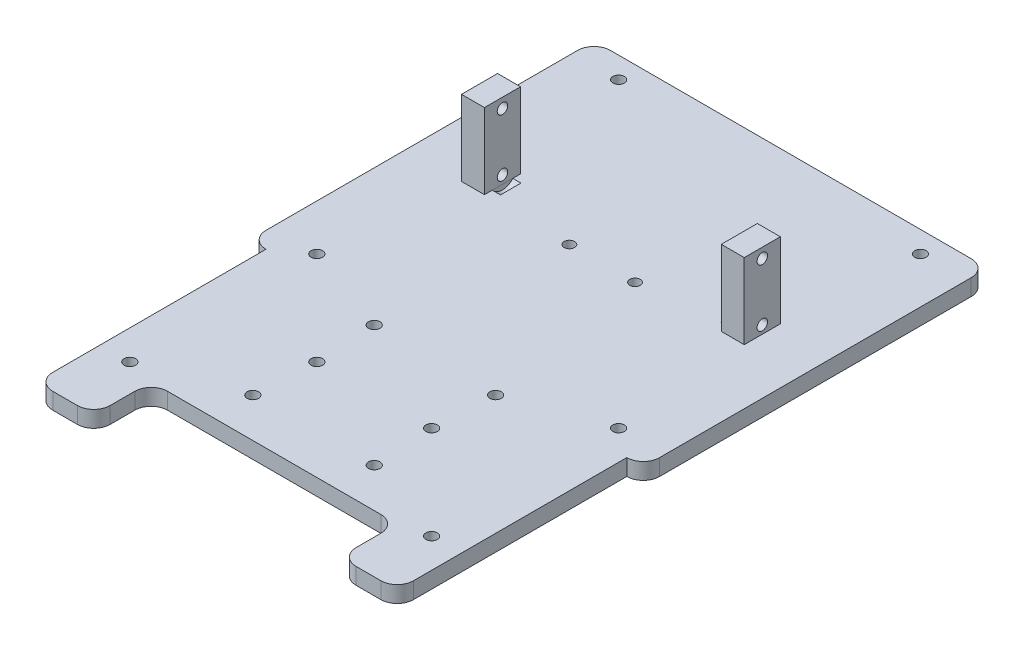
SolidWorks part; units mm, degrees
ref_plane "정면" through (0, 0, 0) normal (0, 0, 1) x (1, 0, 0)
ref_plane "윗면" through (0, 0, 0) normal (0, 1, 0) x (1, 0, 0)
ref_plane "우측면" through (0, 0, 0) normal (1, 0, 0) x (0, 0, -1)
sketch "스케치1" plane through (0, 0, 0) normal (0, 1, 0) x (1, 0, 0)
  line L0 (-55, -52.5) -> (-60, -52.5)
  line L1 (60, 52.5) -> (-60, 52.5)
  line L2 (60, 52.5) -> (60, -52.5)
  line L3 (60, -52.5) -> (55, -52.5)
  line L4 (-60, 52.5) -> (-60, -52.5)
  line L5 (60, 52.5) -> (-60, -52.5) construction
  line L6 (60, -52.5) -> (-60, 52.5) construction
  line L7 (55, -122.5) -> (-55, -122.5)
  line L8 (55, -122.5) -> (55, -52.5)
  line L10 (-55, -122.5) -> (-55, -52.5)
  line L11 (55, -122.5) -> (-55, -52.5) construction
  line L12 (55, -52.5) -> (-55, -122.5) construction
  point P0 (0, 0)
  point P6 (0, -87.5)
  dimension "D1" = 120
  dimension "D2" = 105
  dimension "D3" = 110
  dimension "D4" = 70
extrude "보스-돌출1" add sketch "스케치1" along normal blind 5
sketch "스케치2" plane through (0, 5, 0) normal (0, 1, 0) x (1, 0, 0)
  line L0 (-43.1, 29.5) -> (-43.1, -5.3) construction
  line L1 (-36.1, -4.8) -> (-43.1, -4.8)
  line L2 (-36.1, -4.8) -> (-36.1, 6.2)
  line L3 (-36.1, 6.2) -> (-43.1, 6.2)
  line L4 (-43.1, -4.8) -> (-43.1, 6.2)
  line L5 (-61.9, -0.8) -> (-43.1, -0.8) construction
  line L6 (-43.1, 2.2) -> (-61.9, 2.2) construction
  dimension "D1" = 7
  dimension "D2" = 4
  dimension "D3" = 4
extrude "보스-돌출2" add sketch "스케치2" along normal blind 23 separate body
sketch "스케치3" plane through (-36.1, 0, 0) normal (1, 0, 0) x (0, 0, -1)
  circle A0 centre (0.7, 7.5) radius 1.5 construction
  circle A1 centre (0.7, 25) radius 1.5 construction
  circle A2 centre (0.7, 25) radius 1.6
  circle A3 centre (0.7, 7.5) radius 1.6
  circle A4 centre (0.7, 7.5) radius 1.5 construction
  circle A5 centre (0.7, 25) radius 1.5 construction
  dimension "D1" = 3.2
  dimension "D2" = 3.2
extrude "컷-돌출1" cut sketch "스케치3" against normal through all
mirror "대칭 복사1" about plane through (0, 0, 0) normal (1, 0, 0) of bodies 103
sketch "스케치5" plane through (0, 5, 0) normal (0, 1, 0) x (1, 0, 0)
  circle A0 centre (-46, -46) radius 1.75 construction
  circle A1 centre (-46, 46) radius 1.75 construction
  circle A2 centre (46, 46) radius 1.75 construction
  circle A3 centre (46, -46) radius 1.75 construction
  circle A4 centre (-46, -46) radius 1.75
  circle A5 centre (-46, 46) radius 1.75
  circle A6 centre (46, 46) radius 1.75
  circle A7 centre (46, -46) radius 1.75
extrude "메인보드 홀" cut sketch "스케치5" against normal through all
sketch "Sketch2" plane through (36.1, 0, 0) normal (-1, 0, 0) x (0, 0, 1)
  circle A0 centre (-0.7, 7.5) radius 4
  dimension "D1" = 8
extrude "Cut-Extrude1" cut sketch "Sketch2" along normal blind 2.5
sketch "Sketch3" plane through (-36.1, 0, 0) normal (1, 0, 0) x (0, 0, -1)
  circle A0 centre (0.7, 7.5) radius 4
  dimension "D1" = 8
extrude "Cut-Extrude2" cut sketch "Sketch3" along normal blind 2.5
sketch "Sketch4" plane through (0, 5, 0) normal (0, 1, 0) x (1, 0, 0)
  circle A0 centre (10, -5) radius 1.5 construction
  circle A1 centre (-10, -5) radius 1.5 construction
  circle A2 centre (10, -5) radius 1.5 construction
  circle A3 centre (-10, -5) radius 1.5 construction
  circle A4 centre (-10, -5) radius 1.6
  circle A5 centre (10, -5) radius 1.6
  dimension "D1" = 3.2
  dimension "D2" = 3.2
extrude "배터리홀더 홀" cut sketch "Sketch4" against normal through all and the other way through all
sketch "Sketch6" plane through (0, 5, 0) normal (0, 1, 0) x (1, 0, 0)
  line L1 (-18.5, -93) -> (18.5, -93) construction
  line L2 (-18.5, -93) -> (-18.5, -56) construction
  line L3 (-18.5, -56) -> (18.5, -56) construction
  line L4 (18.5, -93) -> (18.5, -56) construction
  line L5 (-18.5, -93) -> (18.5, -56) construction
  line L6 (-18.5, -56) -> (18.5, -93) construction
  circle A0 centre (-46, -46) radius 1.75 construction
  circle A1 centre (-18.5, -93) radius 1.75
  circle A2 centre (-18.5, -56) radius 1.75
  circle A3 centre (18.5, -56) radius 1.75
  circle A4 centre (18.5, -93) radius 1.75
  point P0 (0, -74.5)
  dimension "D3" = 3.5
  dimension "D1" = 37
  dimension "D2" = 10
extrude "모터드라이버 홀" cut sketch "Sketch6" against normal through all
sketch "Sketch7" plane through (0, 5, 0) normal (0, 1, 0) x (1, 0, 0)
  line L0 (-46, -103) -> (46, -103) construction
  line L1 (0, -103) -> (0, 0) construction
  circle A0 centre (-46, -103) radius 1.75
  circle A1 centre (-18.5, -93) radius 1.75 construction
  circle A2 centre (46, -103) radius 1.75
  dimension "D1" = 3.5
  dimension "D3" = 3.5
  dimension "D2" = 10
  dimension "D4" = 92
extrude "센서보드 홀" cut sketch "Sketch7" against normal through all
sketch "Sketch9" plane through (0, 5, 0) normal (0, 1, 0) x (1, 0, 0)
  line L0 (-17.5, -74.5) -> (17.5, -74.5) construction
  circle A0 centre (-17.5, -74.5) radius 1.75
  circle A1 centre (17.5, -74.5) radius 1.75
  dimension "D2" = 3.5
  dimension "D1" = 35
extrude "볼캐스터 홀" cut sketch "Sketch9" against normal through all
sketch "Sketch8" plane through (0, 5, 0) normal (0, 1, 0) x (1, 0, 0)
  line L0 (-55, -122.5) -> (55, -122.5) construction
  line L1 (-37.5, -140) -> (37.5, -140)
  line L2 (-37.5, -140) -> (-37.5, -105)
  line L3 (-37.5, -105) -> (37.5, -105)
  line L4 (37.5, -140) -> (37.5, -105)
  line L5 (-37.5, -140) -> (37.5, -105) construction
  line L6 (-37.5, -105) -> (37.5, -140) construction
  point P0 (0, -122.5)
  dimension "D1" = 75
  dimension "D2" = 35
extrude "Cut-Extrude7" cut sketch "Sketch8" against normal through all
fillet "필렛1" radius 5 8 edges at (60, 2.5, -52.5) (-60, 2.5, -52.5) (55, 2.5, 122.5) (-55, 2.5, 122.5) (37.5, 2.5, 122.5) (-37.5, 2.5, 122.5) (37.5, 2.5, 105) (-37.5, 2.5, 105)
fillet "Fillet2" radius 5 2 edges at (60, 2.5, 52.5) (-60, 2.5, 52.5)
